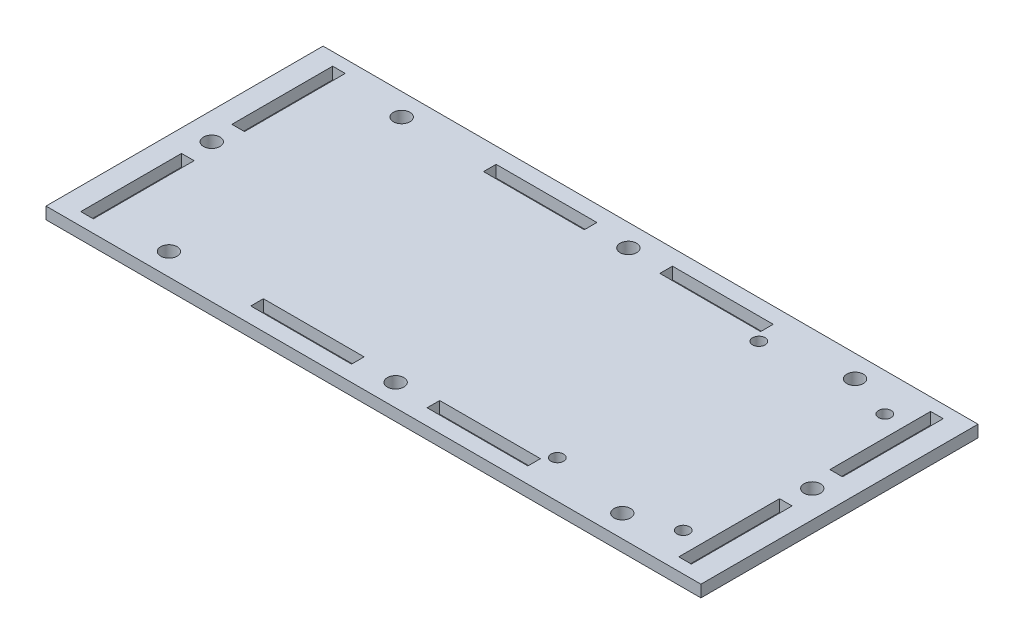
SolidWorks part; units mm, degrees
material "Thornel VCB-20 Carbon Cloth"
ref_plane "Front Plane" through (0, 0, 0) normal (0, 0, 1) x (1, 0, 0)
ref_plane "Top Plane" through (0, 0, 0) normal (0, 1, 0) x (1, 0, 0)
ref_plane "Right Plane" through (0, 0, 0) normal (1, 0, 0) x (0, 0, -1)
sketch "Sketch1" plane through (0, 0, 0) normal (0, 1, 0) x (1, 0, 0)
  line L1 (-82.55, -34.925) -> (82.55, -34.925)
  line L2 (-82.55, -34.925) -> (-82.55, 34.925)
  line L3 (-82.55, 34.925) -> (82.55, 34.925)
  line L4 (82.55, -34.925) -> (82.55, 34.925)
  dimension "D1" = 69.85
  dimension "D2" = 165.1
  dimension "D3" = 34.925
  dimension "D4" = 82.55
extrude "Boss-Extrude1" add sketch "Sketch1" along normal blind 3
sketch "Sketch2" plane through (0, 3, 0) normal (0, 1, 0) x (1, 0, 0)
  line L0 (-82.55, 34.925) -> (-82.55, -34.925) construction
  line L1 (82.55, -34.925) -> (82.55, 34.925) construction
  line L2 (82.55, 34.925) -> (-82.55, 34.925) construction
  line L3 (-82.55, -34.925) -> (82.55, -34.925) construction
  circle A0 centre (-77.47, 29.845) radius 1.5
  circle A1 centre (-77.47, -29.845) radius 1.5
  circle A2 centre (77.47, 29.845) radius 1.5
  circle A3 centre (77.47, -29.845) radius 1.5
  dimension "D1" = 3
  dimension "D2" = 3
  dimension "D3" = 3
  dimension "D4" = 3
  dimension "D5" = 5.08
  dimension "D6" = 5.08
  dimension "D7" = 5.08
  dimension "D8" = 5.08
  dimension "D9" = 5.08
  dimension "D10" = 5.08
  dimension "D11" = 5.08
  dimension "D12" = 5.08
sketch "Sketch3" plane through (0, 3, 0) normal (0, 1, 0) x (1, 0, 0)
  line L0 (-82.55, 34.925) -> (-82.55, -34.925) construction
  line L1 (82.55, -34.925) -> (82.55, 34.925) construction
  line L2 (-82.55, -34.925) -> (82.55, -34.925) construction
  line L3 (82.55, 34.925) -> (-82.55, 34.925) construction
  circle A0 centre (-75.692, 0) radius 2.0828
  circle A1 centre (75.692, 0) radius 2.0828
  circle A2 centre (0, -29.337) radius 2.0828
  circle A3 centre (0, 29.337) radius 2.0828
  circle A4 centre (57.15, 29.337) radius 2.0828
  circle A5 centre (57.15, -29.337) radius 2.0828
  circle A6 centre (-57.15, -29.337) radius 2.0828
  circle A7 centre (-57.15, 29.337) radius 2.0828
  dimension "D1" = 6.858
  dimension "D2" = 6.858
  dimension "D3" = 5.588
  dimension "D4" = 5.588
  dimension "D5" = 2
  dimension "D6" = 2
extrude "Cut-Extrude2" cut sketch "Sketch3" against normal blind 5.08
sketch "Sketch4" plane through (0, 3, 0) normal (0, 1, 0) x (1, 0, 0)
  line L0 (-82.55, 34.925) -> (-82.55, -34.925) construction
  line L1 (-44.31, -29) -> (-67.31, -29) construction
  line L2 (-44.31, -29) -> (-44.31, 29) construction
  line L3 (-44.31, 29) -> (-67.31, 29) construction
  line L4 (-67.31, -29) -> (-67.31, 29) construction
  line L5 (-44.31, -29) -> (-67.31, 29) construction
  line L6 (-44.31, 29) -> (-67.31, -29) construction
  circle A0 centre (-67.31, 29) radius 1.625
  circle A1 centre (-44.31, 29) radius 1.625
  circle A2 centre (-44.31, -29) radius 1.625
  circle A3 centre (-67.31, -29) radius 1.625
  point P0 (-55.81, 0)
  dimension "D3" = 3.25
  dimension "D1" = 58
  dimension "D2" = 23
  dimension "D4" = 15.24
sketch "Sketch5" plane through (0, 3, 0) normal (0, 1, 0) x (1, 0, 0)
  line L0 (82.55, 34.925) -> (-82.55, 34.925) construction
  line L1 (68.58, -25.4) -> (36.83, -25.4) construction
  line L2 (68.58, -25.4) -> (68.58, 25.4) construction
  line L3 (68.58, 25.4) -> (36.83, 25.4) construction
  line L4 (36.83, -25.4) -> (36.83, 25.4) construction
  line L5 (68.58, -25.4) -> (36.83, 25.4) construction
  line L6 (68.58, 25.4) -> (36.83, -25.4) construction
  line L7 (-82.55, -34.925) -> (82.55, -34.925) construction
  line L8 (82.55, -34.925) -> (82.55, 34.925) construction
  circle A0 centre (68.58, -25.4) radius 1.5875
  circle A2 centre (68.58, 25.4) radius 1.5875
  circle A3 centre (36.83, 25.4) radius 1.5875
  circle A4 centre (36.83, -25.4) radius 1.5875
  point P0 (52.705, 0)
  dimension "D1" = 9.525
  dimension "D3" = 3.175
  dimension "D2" = 9.525
  dimension "D4" = 31.75
  dimension "D5" = 13.97
extrude "Cut-Extrude4" cut sketch "Sketch5" against normal blind 7.874
sketch "Sketch6" plane through (0, 3, 0) normal (0, 1, 0) x (1, 0, 0)
  line L0 (82.55, 34.925) -> (-82.55, 34.925) construction
  line L1 (-34.925, 27.7495) -> (-9.525, 27.7495)
  line L2 (-34.925, 27.7495) -> (-34.925, 30.9245)
  line L3 (-34.925, 30.9245) -> (-9.525, 30.9245)
  line L4 (-9.525, 27.7495) -> (-9.525, 30.9245)
  line L5 (-34.925, 27.7495) -> (-9.525, 30.9245) construction
  line L6 (-34.925, 30.9245) -> (-9.525, 27.7495) construction
  line L7 (34.925, 30.9245) -> (34.925, 27.7495)
  line L8 (34.925, 30.9245) -> (9.525, 30.9245)
  line L9 (9.525, 30.9245) -> (9.525, 27.7495)
  line L10 (34.925, 27.7495) -> (9.525, 27.7495)
  line L11 (-34.925, -30.9245) -> (-34.925, -27.7495)
  line L12 (-34.925, -27.7495) -> (-9.525, -27.7495)
  line L13 (-9.525, -30.9245) -> (-9.525, -27.7495)
  line L14 (-34.925, -30.9245) -> (-9.525, -30.9245)
  line L15 (34.925, -27.7495) -> (34.925, -30.9245)
  line L16 (34.925, -27.7495) -> (9.525, -27.7495)
  line L17 (9.525, -27.7495) -> (9.525, -30.9245)
  line L18 (34.925, -30.9245) -> (9.525, -30.9245)
  line L19 (-82.55, 34.925) -> (-82.55, -34.925) construction
  line L20 (-76.962, 31.75) -> (-73.787, 31.75)
  line L21 (-76.962, 31.75) -> (-76.962, 6.35)
  line L22 (-76.962, 6.35) -> (-73.787, 6.35)
  line L23 (-73.787, 31.75) -> (-73.787, 6.35)
  line L24 (-76.962, 31.75) -> (-73.787, 6.35) construction
  line L25 (-76.962, 6.35) -> (-73.787, 31.75) construction
  line L26 (-76.962, -6.35) -> (-76.962, -31.75)
  line L27 (-76.962, -6.35) -> (-73.787, -6.35)
  line L28 (-73.787, -6.35) -> (-73.787, -31.75)
  line L29 (-76.962, -31.75) -> (-73.787, -31.75)
  line L30 (-82.55, -34.925) -> (82.55, -34.925) construction
  line L31 (76.962, -31.75) -> (76.962, -6.35)
  line L32 (76.962, -31.75) -> (73.787, -31.75)
  line L33 (73.787, -31.75) -> (73.787, -6.35)
  line L34 (76.962, -6.35) -> (73.787, -6.35)
  line L35 (76.962, 6.35) -> (76.962, 31.75)
  line L36 (76.962, 31.75) -> (73.787, 31.75)
  line L37 (73.787, 6.35) -> (73.787, 31.75)
  line L38 (76.962, 6.35) -> (73.787, 6.35)
  circle A0 centre (0, 29.337) radius 2.0828 construction
  point P0 (-22.225, 29.337)
  point P9 (-75.3745, 19.05)
  point P16 (0, 29.337)
  point P25 (0, 0)
  point P41 (0, 0)
  point P48 (0, 0)
  dimension "D1" = 5.588
  dimension "D2" = 3.175
  dimension "D3" = 25.4
  dimension "D4" = 22.225
  dimension "D7" = 5.588
  dimension "D8" = 3.175
  dimension "D9" = 25.4
  dimension "D10" = 3.175
  dimension "D12" = 3.175
  dimension "D11" = 2
  dimension "D5" = 2
  dimension "D6" = 2
  dimension "D13" = 2
extrude "Cut-Extrude5" cut sketch "Sketch6" against normal blind 10.922
sketch "Sketch10" plane through (0, 3, 0) normal (0, 1, 0) x (1, 0, 0)
  line L0 (-38.1, 23.495) -> (-19.05, 23.495) construction
  line L1 (-38.1, 24.6856) -> (-19.05, 24.6856)
  line L2 (-38.1, 24.6856) -> (-38.1, 22.3044)
  line L3 (-38.1, 22.3044) -> (-19.05, 22.3044)
  line L4 (-19.05, 24.6856) -> (-19.05, 22.3044)
  line L5 (-28.575, 24.6856) -> (-28.575, 22.3044)
  line L6 (82.55, 34.925) -> (-82.55, 34.925) construction
  line L7 (-82.55, 34.925) -> (-82.55, -34.925) construction
  line L8 (-12.7, 24.6856) -> (-12.7, 22.3044)
  line L9 (-12.7, 24.6856) -> (6.35, 24.6856)
  line L10 (6.35, 24.6856) -> (6.35, 22.3044)
  line L11 (-12.7, 22.3044) -> (6.35, 22.3044)
  line L12 (12.7, 24.6856) -> (12.7, 22.3044)
  line L13 (12.7, 24.6856) -> (31.75, 24.6856)
  line L14 (31.75, 24.6856) -> (31.75, 22.3044)
  line L15 (12.7, 22.3044) -> (31.75, 22.3044)
  line L16 (-12.7, 9.4456) -> (-12.7, 7.0644)
  line L17 (-12.7, 9.4456) -> (6.35, 9.4456)
  line L18 (6.35, 9.4456) -> (6.35, 7.0644)
  line L19 (-12.7, 7.0644) -> (6.35, 7.0644)
  line L20 (12.7, 9.4456) -> (12.7, 7.0644)
  line L21 (12.7, 9.4456) -> (31.75, 9.4456)
  line L22 (31.75, 9.4456) -> (31.75, 7.0644)
  line L23 (12.7, 7.0644) -> (31.75, 7.0644)
  line L24 (-38.1, 9.4456) -> (-38.1, 7.0644)
  line L25 (-38.1, 9.4456) -> (-19.05, 9.4456)
  line L26 (-19.05, 9.4456) -> (-19.05, 7.0644)
  line L27 (-38.1, 7.0644) -> (-19.05, 7.0644)
  line L28 (-38.1, 24.6856) -> (-12.7, 24.6856) construction
  line L29 (0, 0) -> (-82.55, 0) construction
  line L30 (-38.1, -24.6856) -> (-12.7, -24.6856) construction
  line L31 (-38.1, -23.495) -> (-19.05, -23.495) construction
  line L32 (-38.1, -7.0644) -> (-19.05, -7.0644)
  line L33 (-19.05, -9.4456) -> (-19.05, -7.0644)
  line L34 (-38.1, -9.4456) -> (-19.05, -9.4456)
  line L35 (-38.1, -9.4456) -> (-38.1, -7.0644)
  line L36 (12.7, -7.0644) -> (31.75, -7.0644)
  line L37 (31.75, -9.4456) -> (31.75, -7.0644)
  line L38 (12.7, -9.4456) -> (31.75, -9.4456)
  line L39 (12.7, -9.4456) -> (12.7, -7.0644)
  line L40 (-12.7, -7.0644) -> (6.35, -7.0644)
  line L41 (6.35, -9.4456) -> (6.35, -7.0644)
  line L42 (-12.7, -9.4456) -> (6.35, -9.4456)
  line L43 (-12.7, -9.4456) -> (-12.7, -7.0644)
  line L44 (12.7, -22.3044) -> (31.75, -22.3044)
  line L45 (31.75, -24.6856) -> (31.75, -22.3044)
  line L46 (12.7, -24.6856) -> (31.75, -24.6856)
  line L47 (12.7, -24.6856) -> (12.7, -22.3044)
  line L48 (-12.7, -22.3044) -> (6.35, -22.3044)
  line L49 (6.35, -24.6856) -> (6.35, -22.3044)
  line L50 (-12.7, -24.6856) -> (6.35, -24.6856)
  line L51 (-12.7, -24.6856) -> (-12.7, -22.3044)
  line L52 (-28.575, -24.6856) -> (-28.575, -22.3044)
  line L53 (-19.05, -24.6856) -> (-19.05, -22.3044)
  line L54 (-38.1, -22.3044) -> (-19.05, -22.3044)
  line L55 (-38.1, -24.6856) -> (-38.1, -22.3044)
  line L56 (-38.1, -24.6856) -> (-19.05, -24.6856)
  line L57 (8.7313, 11.1125) -> (8.7313, 20.6375)
  line L58 (-16.6687, 11.1125) -> (-15.0812, 11.1125)
  line L59 (-16.6687, 11.1125) -> (-16.6687, 20.6375)
  line L60 (-16.6687, 20.6375) -> (-15.0812, 20.6375)
  line L61 (-15.0812, 11.1125) -> (-15.0812, 20.6375)
  line L62 (-16.6687, 11.1125) -> (-15.0812, 20.6375) construction
  line L63 (-16.6687, 20.6375) -> (-15.0812, 11.1125) construction
  line L64 (8.7313, 11.1125) -> (10.3188, 11.1125)
  line L65 (10.3188, 11.1125) -> (10.3188, 20.6375)
  line L66 (8.7313, 20.6375) -> (10.3188, 20.6375)
  line L67 (-16.6687, 11.1125) -> (8.7313, 11.1125) construction
  line L68 (-16.6687, -20.6375) -> (-15.0812, -20.6375)
  line L69 (-15.0812, -11.1125) -> (-15.0812, -20.6375)
  line L70 (-16.6687, -11.1125) -> (-15.0812, -11.1125)
  line L71 (-16.6687, -11.1125) -> (-16.6687, -20.6375)
  line L72 (8.7313, -11.1125) -> (10.3188, -11.1125)
  line L73 (10.3188, -11.1125) -> (10.3188, -20.6375)
  line L74 (8.7313, -20.6375) -> (10.3188, -20.6375)
  line L75 (8.7313, -11.1125) -> (8.7313, -20.6375)
  line L76 (43.0033, 24.8834) -> (43.0033, 22.5021)
  line L77 (43.0033, 24.8834) -> (62.0533, 24.8834)
  line L78 (62.0533, 24.8834) -> (62.0533, 22.5021)
  line L79 (43.0033, 22.5021) -> (62.0533, 22.5021)
  line L80 (43.0033, 9.6434) -> (43.0033, 7.2621)
  line L81 (43.0033, 9.6434) -> (62.0533, 9.6434)
  line L82 (62.0533, 9.6434) -> (62.0533, 7.2621)
  line L83 (43.0033, 7.2621) -> (62.0533, 7.2621)
  line L84 (17.6033, 24.8834) -> (43.0033, 24.8834) construction
  line L85 (55.7033, 0.1978) -> (-26.8467, 0.1978) construction
  line L86 (17.6033, -24.4879) -> (43.0033, -24.4879) construction
  line L87 (43.0033, -6.8666) -> (62.0533, -6.8666)
  line L88 (62.0533, -9.2479) -> (62.0533, -6.8666)
  line L89 (43.0033, -9.2479) -> (62.0533, -9.2479)
  line L90 (43.0033, -9.2479) -> (43.0033, -6.8666)
  line L91 (43.0033, -22.1066) -> (62.0533, -22.1066)
  line L92 (62.0533, -24.4879) -> (62.0533, -22.1066)
  line L93 (43.0033, -24.4879) -> (62.0533, -24.4879)
  line L94 (43.0033, -24.4879) -> (43.0033, -22.1066)
  line L95 (64.4346, 11.3103) -> (64.4346, 20.8353)
  line L96 (39.0346, 11.3103) -> (40.6221, 11.3103)
  line L97 (39.0346, 11.3103) -> (39.0346, 20.8353)
  line L98 (39.0346, 20.8353) -> (40.6221, 20.8353)
  line L99 (40.6221, 11.3103) -> (40.6221, 20.8353)
  line L100 (39.0346, 11.3103) -> (40.6221, 20.8353) construction
  line L101 (39.0346, 20.8353) -> (40.6221, 11.3103) construction
  line L102 (64.4346, 11.3103) -> (66.0221, 11.3103)
  line L103 (66.0221, 11.3103) -> (66.0221, 20.8353)
  line L104 (64.4346, 20.8353) -> (66.0221, 20.8353)
  line L105 (39.0346, 11.3103) -> (64.4346, 11.3103) construction
  line L106 (39.0346, -20.4397) -> (40.6221, -20.4397)
  line L107 (40.6221, -10.9147) -> (40.6221, -20.4397)
  line L108 (39.0346, -10.9147) -> (40.6221, -10.9147)
  line L109 (39.0346, -10.9147) -> (39.0346, -20.4397)
  line L110 (64.4346, -10.9147) -> (66.0221, -10.9147)
  line L111 (66.0221, -10.9147) -> (66.0221, -20.4397)
  line L112 (64.4346, -20.4397) -> (66.0221, -20.4397)
  line L113 (64.4346, -10.9147) -> (64.4346, -20.4397)
  point P65 (-15.875, 15.875)
  point P105 (39.8283, 16.0728)
  dimension "D1" = 19.05
  dimension "D2" = 2.3813
  dimension "D3" = 11.43
  dimension "D4" = 44.45
  dimension "D7" = 25.4
  dimension "D8" = 15.24
  dimension "D9" = 1.5875
  dimension "D10" = 3.175
  dimension "D11" = 9.525
  dimension "D12" = 7.62
  dimension "D14" = 25.4
  dimension "D15" = 25.4
  dimension "D16" = 1.5875
  dimension "D17" = 9.525
  dimension "D18" = 25.4
  dimension "D5" = 3
  dimension "D6" = 2
  dimension "D13" = 2
